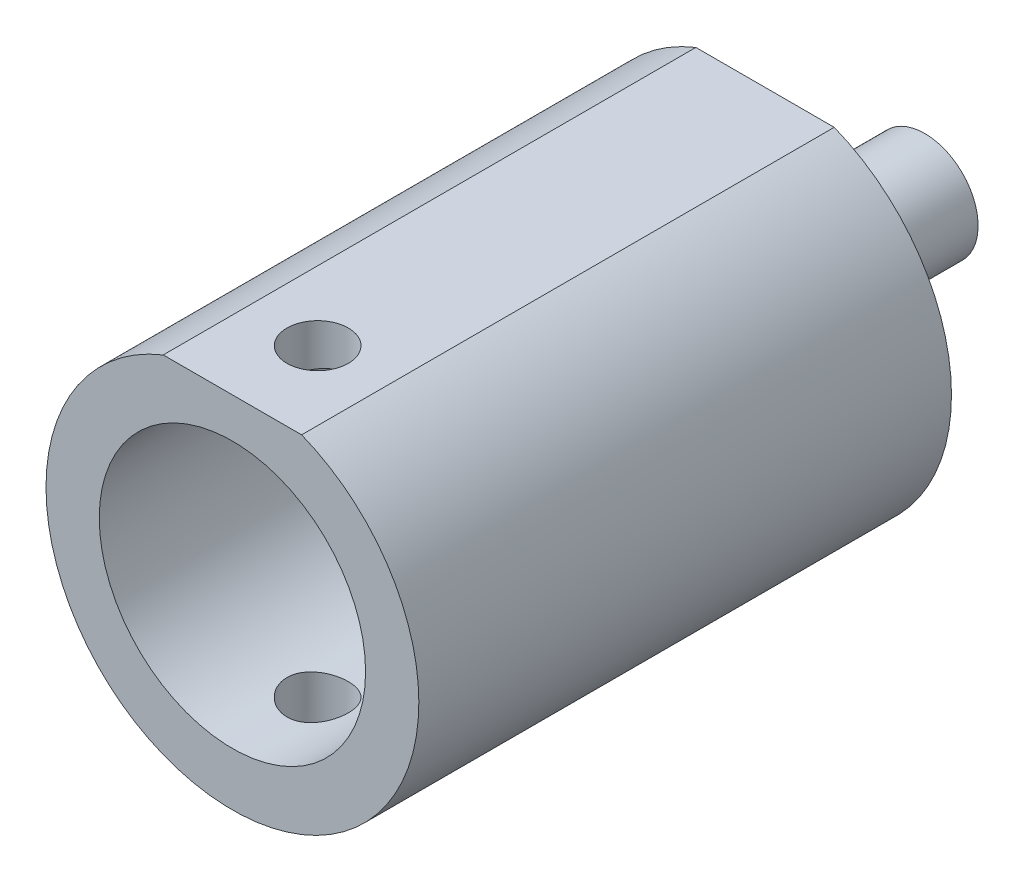
SolidWorks part; units mm, degrees
ref_plane "Front Plane" through (0, 0, 0) normal (0, 0, 1) x (1, 0, 0)
ref_plane "Top Plane" through (0, 0, 0) normal (0, 1, 0) x (1, 0, 0)
ref_plane "Right Plane" through (0, 0, 0) normal (1, 0, 0) x (0, 0, -1)
sketch "Sketch1" plane through (0, 0, 0) normal (0, 1, 0) x (1, 0, 0)
  line L6 (0, 0) -> (7.9375, 0)
  line L7 (7.9375, 0) -> (11.1125, 0)
  line L8 (11.1125, 0) -> (11.1125, 31.75)
  line L9 (11.1125, 31.75) -> (3.175, 31.75)
  line L10 (3.175, 31.75) -> (3.175, 41.275)
  line L11 (3.175, 41.275) -> (0, 41.275)
  line L12 (0, 41.275) -> (0, 25.4)
  line L13 (0, 25.4) -> (0, 0)
  line L14 (0, 25.4) -> (7.9375, 25.4) construction
  line L15 (7.9375, 25.4) -> (7.9375, 0) construction
  dimension "D1" = 3.175
  dimension "D2" = 7.9375
  dimension "D3" = 6.35
  dimension "D4" = 25.4
  dimension "D5" = 9.525
revolve "Revolve1" add sketch "Sketch1" angle 360 about L13
hole_wizard "5/8 (0.625) Diameter Hole1" positions "Sketch6" profile "Sketch7" hole size "5/8" standard "ANSI Inch"
sketch "Sketch6" plane through (0, 0, 0) normal (0, 0, 1) x (1, 0, 0)
  point P0 (0, 0)
sketch "Sketch7" plane through (0, 0, 0) normal (1, 0, 0) x (0, -1, 0)
  line L0 (0, 0) -> (0, 30.1693)
  line L1 (0, 30.1693) -> (7.9375, 25.4)
  line L2 (7.9375, 25.4) -> (7.9375, 0)
  line L5 (7.9375, 0) -> (0, 0)
  line L10 (0, 30.1693) -> (-7.9375, 25.4) construction
  line L11 (0, -6.35) -> (0, 107.95) construction
  dimension "Hole Dia." = 15.875
  dimension "Hole Depth" = 25.4
  dimension "Drill Angle" = 118
sketch "Sketch3" plane through (0, 0, 0) normal (1, 0, 0) x (0, 0, -1)
  line L0 (0, 10.3188) -> (0, 11.1125)
  line L1 (0, 11.1125) -> (0, -11.1125) construction
  line L2 (0, 11.1125) -> (31.75, 11.1125)
  line L3 (31.75, 11.1125) -> (31.75, 10.3188)
  line L4 (31.75, -11.1125) -> (31.75, 11.1125) construction
  line L5 (31.75, 10.3188) -> (0, 10.3188)
  dimension "D1" = 0.7937
extrude "Cut-Extrude1" cut sketch "Sketch3" against normal through all both and the other way through all
hole_wizard "#6 Clearance Hole1" positions "Sketch4" profile "Sketch5" hole size "#6" standard "ANSI Inch" end condition through all
sketch "Sketch4" plane through (0, 10.3188, 0) normal (0, 1, 0) x (1, 0, 0)
  line L1 (7.9375, 25.4) -> (-7.9375, 25.4) construction
  point P0 (0, 5.08)
  point P12 (-1.6561, 34.5075)
  dimension "D1" = 20.32
sketch "Sketch5" plane through (0, 10.3188, -5.08) normal (1, 0, 0) x (0, 0, 1)
  line L0 (0, 0) -> (0, 21.4313)
  line L1 (0, 21.4313) -> (1.8288, 21.4313)
  line L2 (1.8288, 21.4313) -> (1.8288, 0)
  line L5 (1.8288, 0) -> (0, 0)
  line L11 (0, -6.35) -> (0, 107.95) construction
  dimension "Thru Hole Dia." = 3.6576
  dimension "Thru Hole Depth" = 21.4313
